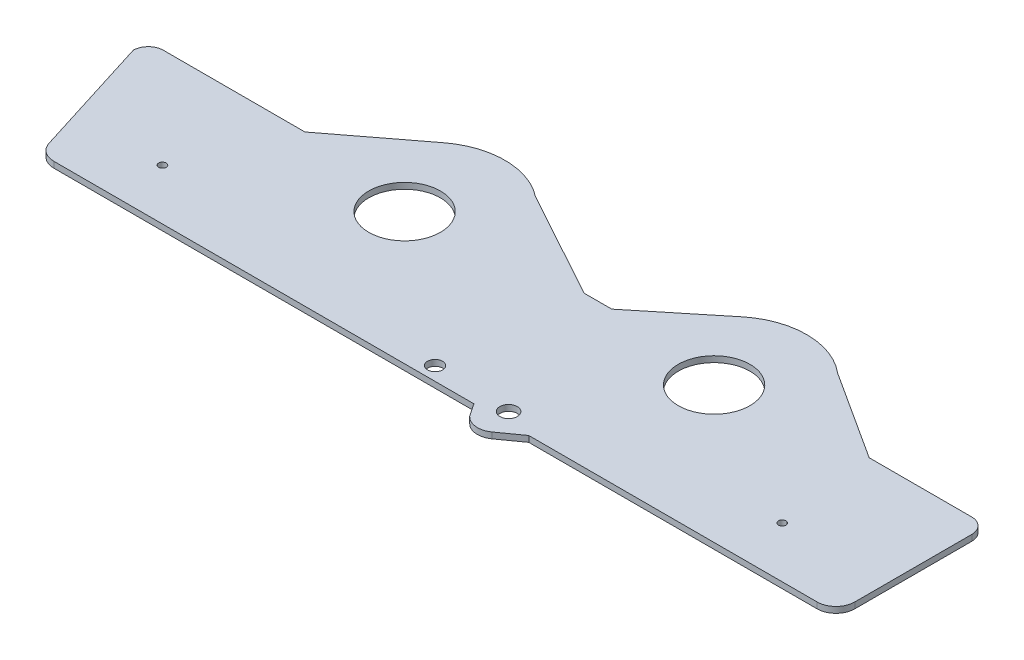
SolidWorks part; units mm, degrees
ref_plane "Front" through (0, 0, 0) normal (0, 0, 1) x (1, 0, 0)
ref_plane "Top" through (0, 0, 0) normal (0, 1, 0) x (1, 0, 0)
ref_plane "Right" through (0, 0, 0) normal (1, 0, 0) x (0, 0, -1)
sketch "Sketch1" plane through (0, 0, 0) normal (0, 1, 0) x (1, 0, 0)
  line L0 (0, 142) -> (42, 8)
  line L1 (0, 0) -> (444.5, 0)
  line L2 (0, 0) -> (0, 150)
  line L3 (0, 150) -> (444.5, 150)
  line L4 (444.5, 0) -> (444.5, 150)
  circle A0 centre (8, 142) radius 8
  circle A1 centre (50, 8) radius 8
  circle A2 centre (436.5, 142) radius 8
  circle A3 centre (436.5, 8) radius 8
  circle A5 centre (265.3381, 75.6339) radius 4.6
  dimension "D3" = 8
  dimension "D5" = 8
  dimension "D7" = 8
  dimension "D9" = 8
  dimension "D1" = 150
  dimension "D2" = 444.5
  dimension "D4" = 8
  dimension "D6" = 50
  dimension "D8" = 8
  dimension "D10" = 8
extrude "Boss-Extrude1" add sketch "Sketch1" along normal blind 3.175 contours A3 L4 A2 L3 A0 L0 A1 L1 | A1 | A0 L0 | A2 | A3 region at (8.0436, 0, -142.0137) region at (232.4974, 0, -76.3855) region at (50, 0, -8) region at (436.5, 0, -142) region at (436.5, 0, -8)
sketch "Sketch2" plane through (0, 0, 0) normal (0, 0, 1) x (1, 0, 0)
  line L1 (-78.5546, 38.0306) -> (518.9117, 38.0306)
  line L2 (-78.5546, 38.0306) -> (-78.5546, -22.9419)
  line L3 (-78.5546, -22.9419) -> (518.9117, -22.9419)
  line L4 (518.9117, 38.0306) -> (518.9117, -22.9419)
extrude "Cut-Extrude1" cut sketch "Sketch2" against normal blind 70
fillet "Fillet1" radius 10 1 edges at (22.5672, 1.5875, -70)
fillet "Fillet2" radius 10 1 edges at (444.5, 1.5875, -70)
sketch "Sketch3" plane through (0, 3.175, 0) normal (0, 1, 0) x (1, 0, 0)
  line L0 (444.5, 80) -> (444.5, 142) construction
  line L1 (29.9125, 70) -> (434.5, 70) construction
  circle A0 centre (224.75, 77.255) radius 3.9908
  dimension "D1" = 219.75
  dimension "D2" = 7.255
extrude "Cut-Extrude2" cut sketch "Sketch3" against normal blind 10
sketch "Sketch4" plane through (0, 3.175, 0) normal (0, 1, 0) x (1, 0, 0)
  line L0 (29.9125, 70) -> (434.5, 70) construction
  line L1 (444.5, 80) -> (444.5, 142) construction
  circle A0 centre (60.5, 97) radius 2
  dimension "D3" = 4
  dimension "D1" = 27
  dimension "D2" = 384
extrude "Cut-Extrude3" cut sketch "Sketch4" against normal through all
sketch "Sketch5" plane through (0, 3.175, 0) normal (0, 1, 0) x (1, 0, 0)
  line L0 (444.5, 80) -> (444.5, 142) construction
  line L1 (29.9125, 70) -> (434.5, 70) construction
  circle A0 centre (389, 97) radius 2
  dimension "D1" = 55.5
  dimension "D3" = 4
  dimension "D2" = 27
extrude "Cut-Extrude4" cut sketch "Sketch5" against normal blind 10
sketch "Sketch6" plane through (0, 0, 0) normal (0, 1, 0) x (1, 0, 0)
  circle A0 centre (149, 150.0404) radius 40
  dimension "D1" = 80
  dimension "D2" = 141
extrude "Boss-Extrude2" add sketch "Sketch6" along normal blind 3.175
sketch "Sketch7" plane through (0, 0, 0) normal (0, 1, 0) x (1, 0, 0)
  line L0 (124.1645, 181.3964) -> (82.7029, 149.7505)
  line L1 (173.8355, 181.3964) -> (231.4689, 149.7505)
  line L2 (82.7029, 149.7505) -> (231.4689, 149.7505)
  line L3 (124.1645, 181.3964) -> (173.8355, 181.3964)
  arc A0 (189, 150) -> (109, 150) centre (149, 150.0404) ccw construction
extrude "Boss-Extrude3" add sketch "Sketch7" along normal blind 3.175
sketch "Sketch9" plane through (0, 0, 0) normal (0, 1, 0) x (1, 0, 0)
  line L0 (444.5, 80) -> (444.5, 142) construction
  line L1 (231.0146, 150) -> (436.5, 150) construction
  line L2 (283.7342, 181.0103) -> (245.6734, 150)
  line L3 (245.6734, 150) -> (269, 150)
  line L4 (334.2658, 181.0103) -> (397.5744, 150)
  circle A0 centre (309, 150) radius 40
  dimension "D1" = 135.5
  dimension "D2" = 0
extrude "Boss-Extrude4" add sketch "Sketch9" along normal blind 3.175 contours A0 L2 L3 | A0 region at (263.2337, 0, -158.4181) region at (309, 0, -150)
sketch "Sketch12" plane through (0, 0, 0) normal (0, 1, 0) x (1, 0, 0)
  line L0 (326.1663, 186.1292) -> (382.1065, 150)
  line L1 (349, 150) -> (436.5, 150) construction
  line L2 (382.1065, 150) -> (340.3988, 150)
  line L3 (340.3988, 150) -> (326.1663, 186.1292)
  arc A0 (349, 150) -> (283.7342, 181.0103) centre (309, 150) ccw construction
extrude "Boss-Extrude6" add sketch "Sketch12" along normal blind 3.175
sketch "Sketch13" plane through (0, 3.175, 0) normal (0, 1, 0) x (1, 0, 0)
  circle A0 centre (146, 139.8404) radius 19
  arc A1 (173.8355, 181.3964) -> (124.1645, 181.3964) centre (149, 150.0404) ccw construction
  point P5 (149, 190.0404)
  dimension "D1" = 50.2
  dimension "D3" = 38
  dimension "D2" = 138
extrude "Cut-Extrude5" cut sketch "Sketch13" against normal blind 10
sketch "Sketch14" plane through (0, 3.175, 0) normal (0, 1, 0) x (1, 0, 0)
  circle A0 centre (307.6065, 142.2981) radius 19
  arc A2 (334.871, 180.5072) -> (283.7342, 181.0103) centre (309, 150) ccw construction
  point P6 (309.3935, 189.9981)
  dimension "D1" = 74.5
  dimension "D3" = 38
  dimension "D2" = 47.7
extrude "Cut-Extrude6" cut sketch "Sketch14" against normal blind 10
sketch "Sketch15" plane through (0, 3.175, 0) normal (0, 1, 0) x (1, 0, 0)
  line L0 (444.5, 80) -> (444.5, 142) construction
  line L2 (231.0146, 150) -> (245.6734, 150) construction
  line L3 (281.6714, 70) -> (270.3236, 61.8707)
  line L4 (29.9125, 70) -> (434.5, 70) construction
  line L5 (264.5, 80) -> (251.9232, 70.9902)
  line L6 (264.5, 80) -> (281.6714, 70)
  line L7 (251.9232, 70.9902) -> (257.164, 63.2042)
  circle A0 centre (264.5, 70) radius 10
  line M13 (29.9125, 70) -> (434.5, 70)
  dimension "D1" = 180
  dimension "D3" = 20
  dimension "D2" = 80
extrude "Boss-Extrude7" add sketch "Sketch15" along normal blind 10 and the other way blind 3.175 contours A0 M13 | A0 M13 | A0 M13 region at (276.3191, 3.175, -67.7653) region at (264.5129, 3.175, -65.7579) region at (254.033, 3.175, -68.7371)
sketch "Sketch16" plane through (0, 13.175, 0) normal (0, 1, 0) x (1, 0, 0)
  line L1 (247.445, 85.003) -> (286.8256, 85.003)
  line L2 (247.445, 85.003) -> (247.445, 51.0981)
  line L3 (247.445, 51.0981) -> (286.8256, 51.0981)
  line L4 (286.8256, 85.003) -> (286.8256, 51.0981)
extrude "Cut-Extrude7" cut sketch "Sketch16" against normal blind 10
